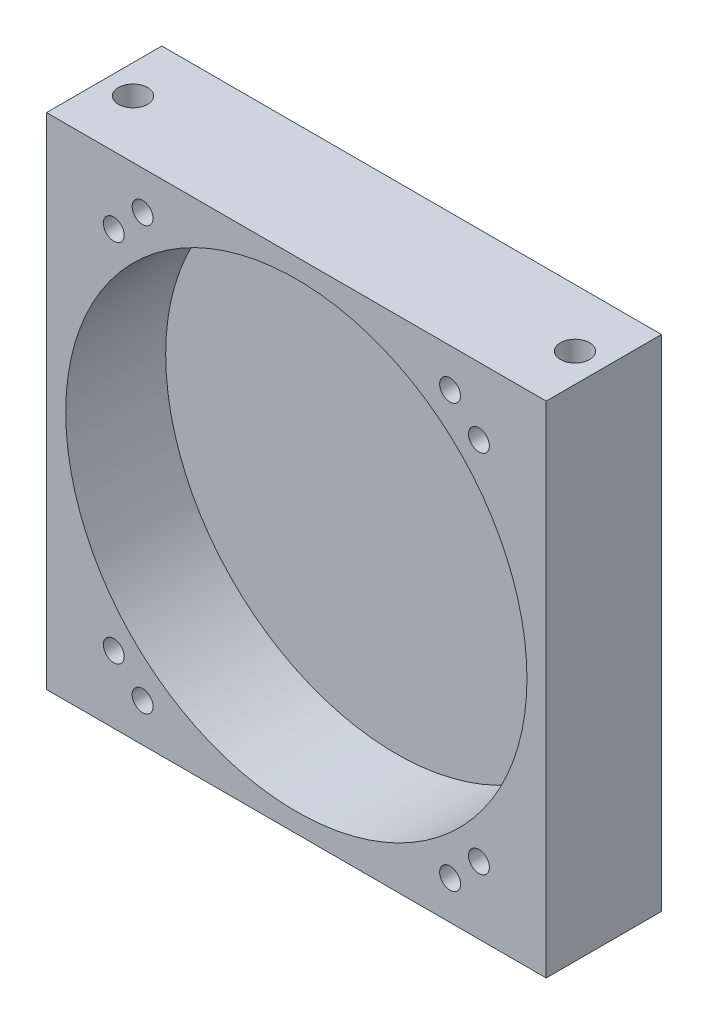
SolidWorks part; units mm, degrees
material "6061-T6 (SS)"
ref_plane "Front Plane" through (0, 0, 0) normal (0, 0, 1) x (1, 0, 0)
ref_plane "Top Plane" through (0, 0, 0) normal (0, 1, 0) x (1, 0, 0)
ref_plane "Right Plane" through (0, 0, 0) normal (1, 0, 0) x (0, 0, -1)
sketch "Sketch1" plane through (0, 0, 0) normal (0, 0, 1) x (1, 0, 0)
  line L1 (41.275, -41.275) -> (-41.275, -41.275)
  line L2 (41.275, -41.275) -> (41.275, 41.275)
  line L3 (41.275, 41.275) -> (-41.275, 41.275)
  line L4 (-41.275, -41.275) -> (-41.275, 41.275)
  line L5 (41.275, -41.275) -> (-41.275, 41.275) construction
  line L6 (41.275, 41.275) -> (-41.275, -41.275) construction
  point P0 (0, 0)
  dimension "D1" = 82.55
  dimension "D2" = 82.55
extrude "Boss-Extrude1" add sketch "Sketch1" along normal blind 19.05
sketch "Sketch2" plane through (0, 0, 19.05) normal (0, 0, 1) x (1, 0, 0)
  circle A0 centre (0, 0) radius 38.1
  dimension "D1" = 76.2
extrude "Cut-Extrude1" cut sketch "Sketch2" against normal blind 16.51
hole_wizard "#10-32 Tapped Hole1" positions "Sketch4" profile "Sketch3" tap size "#10-32" standard "ANSI Inch"
sketch "Sketch4" plane through (0, 41.275, 0) normal (0, 1, 0) x (-1, 0, 0)
  line L0 (-36.5125, 9.525) -> (0, 0) construction
  line L1 (0, 0) -> (36.5125, 9.525) construction
  line L3 (-41.275, 0) -> (41.275, 0) construction
  point P0 (36.5125, 9.525)
  point P1 (-36.5125, 9.525)
  dimension "D1" = 73.025
  dimension "D2" = 9.525
sketch "Sketch3" plane through (-36.5125, 41.275, 9.525) normal (1, 0, 0) x (0, 0, 1)
  line L0 (0, 0) -> (0, 20.2633)
  line L1 (0, 20.2633) -> (2.0193, 19.05)
  line L2 (2.0193, 19.05) -> (2.0193, 18.288)
  line L3 (2.0193, 18.288) -> (2.413, 18.288)
  line L4 (2.413, 18.288) -> (2.413, 0)
  line L5 (2.413, 0) -> (0, 0)
  line L10 (0, 20.2633) -> (-2.0193, 19.05) construction
  line L11 (0, -6.35) -> (0, 107.95) construction
  dimension "Tap Drill Dia." = 4.0386
  dimension "Tap Drill Depth" = 19.05
  dimension "Thread Major Dia." = 4.826
  dimension "Thread Depth" = 18.288
  dimension "Drill Angle" = 118
mirror "Mirror1" about plane through (0, 0, 0) normal (0, 1, 0) of "#10-32 Tapped Hole1"
hole_wizard "#8-32 Tapped Hole1" positions "Sketch6" profile "Sketch5" tap size "#8-32" standard "ANSI Inch"
sketch "Sketch6" plane through (0, 0, 19.05) normal (0, 0, 1) x (1, 0, 0)
  line L0 (25.4, -34.925) -> (-25.4, 34.925) construction
  line L3 (25.4, 34.925) -> (-25.4, -34.925) construction
  point P0 (25.4, -34.925)
  point P1 (-25.4, -34.925)
  point P3 (-25.4, 34.925)
  point P5 (25.4, 34.925)
  dimension "D1" = 50.8
  dimension "D2" = 69.85
sketch "Sketch5" plane through (25.4, -34.925, 19.05) normal (1, 0, 0) x (0, -1, 0)
  line L0 (0, 0) -> (0, 17.0398)
  line L1 (0, 17.0398) -> (1.7272, 16.002)
  line L2 (1.7272, 16.002) -> (1.7272, 0)
  line L5 (1.7272, 0) -> (0, 0)
  line L10 (0, 17.0398) -> (-1.7272, 16.002) construction
  line L11 (0, -6.35) -> (0, 107.95) construction
  dimension "Tap Drill Dia." = 3.4544
  dimension "Tap Drill Depth" = 16.002
  dimension "Drill Angle" = 118
cosmetic thread "Hole Thread1" parameters "D1"=8.382, "D2"=4.1656
cosmetic thread "Hole Thread2" parameters "D1"=8.382, "D2"=4.1656
cosmetic thread "Hole Thread3" parameters "D1"=8.382, "D2"=4.1656
cosmetic thread "Hole Thread4" parameters "D1"=8.382, "D2"=4.1656
hole_wizard "#8-32 Tapped Hole2" positions "Sketch8" profile "Sketch7" tap size "#8-32" standard "ANSI Inch"
sketch "Sketch8" plane through (0, 0, 19.05) normal (0, 0, 1) x (1, 0, 0)
  line L1 (-30.1625, 30.1625) -> (30.1625, 30.1625)
  line L2 (-30.1625, 30.1625) -> (-30.1625, -30.1625)
  line L3 (-30.1625, -30.1625) -> (30.1625, -30.1625)
  line L4 (30.1625, 30.1625) -> (30.1625, -30.1625)
  line L5 (-30.1625, 30.1625) -> (30.1625, -30.1625) construction
  line L6 (-30.1625, -30.1625) -> (30.1625, 30.1625) construction
  point P2 (30.1625, -30.1625)
  point P79 (-30.1625, 30.1625)
  point P80 (-30.1625, -30.1625)
  point P81 (30.1625, 30.1625)
  dimension "D1" = 60.325
  dimension "D2" = 60.325
sketch "Sketch7" plane through (30.1625, -30.1625, 19.05) normal (1, 0, 0) x (0, -1, 0)
  line L0 (0, 0) -> (0, 17.0398)
  line L1 (0, 17.0398) -> (1.7272, 16.002)
  line L2 (1.7272, 16.002) -> (1.7272, 0)
  line L5 (1.7272, 0) -> (0, 0)
  line L10 (0, 17.0398) -> (-1.7272, 16.002) construction
  line L11 (0, -6.35) -> (0, 107.95) construction
  dimension "Tap Drill Dia." = 3.4544
  dimension "Tap Drill Depth" = 16.002
  dimension "Drill Angle" = 118
cosmetic thread "Hole Thread5" parameters "D1"=8.382, "D2"=4.1656
cosmetic thread "Hole Thread6" parameters "D1"=8.382, "D2"=4.1656
cosmetic thread "Hole Thread7" parameters "D1"=8.382, "D2"=4.1656
cosmetic thread "Hole Thread8" parameters "D1"=8.382, "D2"=4.1656
